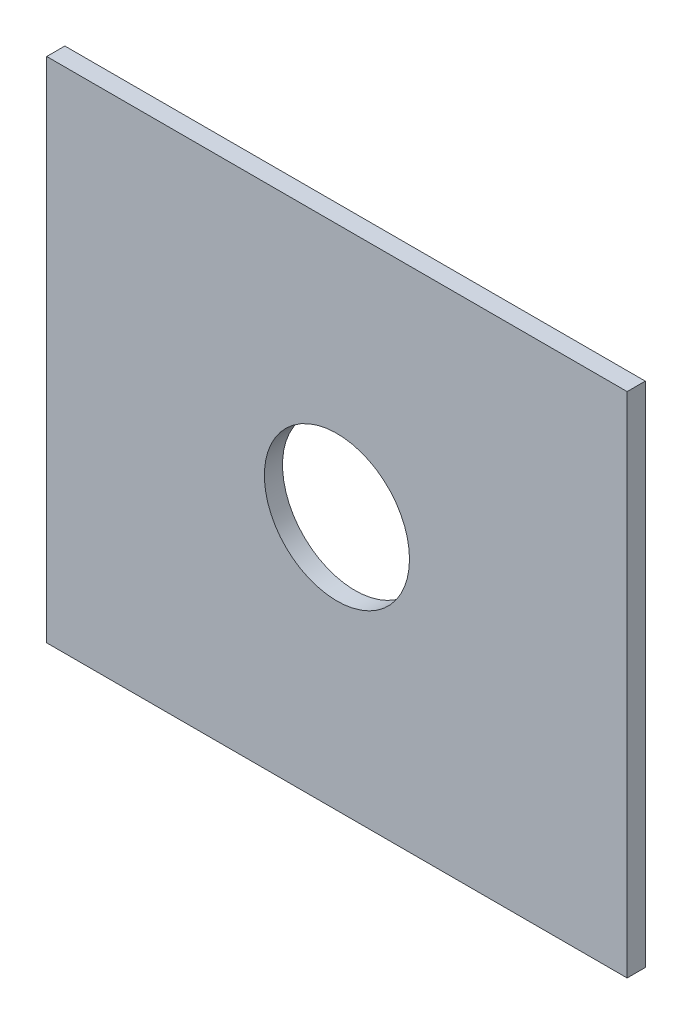
SolidWorks part; units mm, degrees
ref_plane "Front" through (0, 0, 0) normal (0, 0, 1) x (1, 0, 0)
ref_plane "Top" through (0, 0, 0) normal (0, 1, 0) x (1, 0, 0)
ref_plane "Right" through (0, 0, 0) normal (1, 0, 0) x (0, 0, -1)
sketch "Sketch1" plane through (0, 0, 0) normal (0, 0, 1) x (1, 0, 0)
  line L1 (25.4, 7.9375) -> (-25.4, 7.9375)
  line L2 (25.4, 7.9375) -> (25.4, 52.3875)
  line L3 (25.4, 52.3875) -> (-25.4, 52.3875)
  line L4 (-25.4, 7.9375) -> (-25.4, 52.3875)
  line L5 (-25.4, 30.1625) -> (25.4, 30.1625) construction
  circle A0 centre (0, 30.1625) radius 7.9375 construction
  point P8 (0, 30.1625)
  dimension "D1" = 44.45
  dimension "D2" = 50.8
extrude "Extrude1" add sketch "Sketch1" along normal blind 1.5875
sketch "Sketch2" plane through (0, 0, 1.5875) normal (0, 0, 1) x (1, 0, 0)
  circle A0 centre (0, 30.1625) radius 6.35
  circle A1 centre (0, 30.1625) radius 7.9375 construction
  dimension "D1" = 12.7
extrude "Cut-Extrude1" cut sketch "Sketch2" against normal through all
